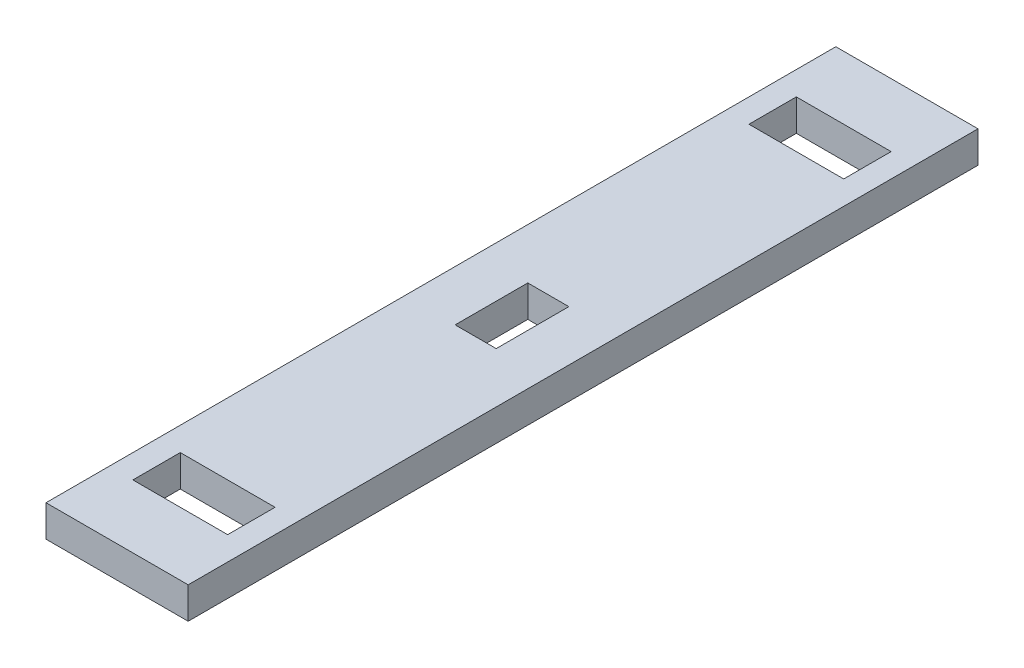
SolidWorks part; units mm, degrees
ref_plane "Plan de face" through (0, 0, 0) normal (0, 0, 1) x (1, 0, 0)
ref_plane "Plan de dessus" through (0, 0, 0) normal (0, 1, 0) x (1, 0, 0)
ref_plane "Plan de droite" through (0, 0, 0) normal (1, 0, 0) x (0, 0, -1)
sketch "Esquisse1" plane through (0, 0, 0) normal (0, 1, 0) x (1, 0, 0)
  line L0 (3.409, -1.8775) -> (3.409, 2.1225) construction
  line L1 (-1.091, 48.1225) -> (7.909, 48.1225)
  line L2 (-1.091, 48.1225) -> (-1.091, -1.8775)
  line L3 (-1.091, -1.8775) -> (7.909, -1.8775)
  line L4 (7.909, 48.1225) -> (7.909, -1.8775)
  line L5 (0.409, 2.1225) -> (6.409, 2.1225)
  line L6 (0.409, 2.1225) -> (0.409, 5.1225)
  line L7 (0.409, 5.1225) -> (6.409, 5.1225)
  line L8 (6.409, 2.1225) -> (6.409, 5.1225)
  line L9 (-1.091, 23.1225) -> (7.909, 23.1225) construction
  line L10 (0.409, 41.1225) -> (6.409, 41.1225)
  line L11 (6.409, 44.1225) -> (6.409, 41.1225)
  line L12 (0.409, 44.1225) -> (6.409, 44.1225)
  line L13 (0.409, 44.1225) -> (0.409, 41.1225)
  dimension "D1" = 50
  dimension "D2" = 9
  dimension "D3" = 4
  dimension "D4" = 6
  dimension "D5" = 3
extrude "Boss.-Extru.1" add sketch "Esquisse1" along normal blind 2 contours L4 L1 L2 L3 L13 L12 L11 L10 L8 L5 L6 L7 region at (3.409, 0, -23.1225)
sketch "Esquisse2" plane through (0, 0, 0) normal (0, -1, 0) x (1, 0, 0)
  line L0 (-1.091, -23.1225) -> (7.909, -23.1225) construction
  line L1 (-1.091, -48.1225) -> (-1.091, 1.8775) construction
  line L2 (7.909, -48.1225) -> (7.909, 1.8775) construction
  line L4 (4.709, -25.4225) -> (2.109, -25.4225)
  line L5 (4.709, -25.4225) -> (4.709, -20.8225)
  line L6 (4.709, -20.8225) -> (2.109, -20.8225)
  line L7 (2.109, -25.4225) -> (2.109, -20.8225)
  line L8 (4.709, -25.4225) -> (2.109, -20.8225) construction
  line L9 (4.709, -20.8225) -> (2.109, -25.4225) construction
  point P6 (3.409, -23.1225)
  point P11 (3.409, -23.1225)
  dimension "D1" = 4.6
  dimension "D2" = 2.6
extrude "Enlèv. mat.-Extru.1" cut sketch "Esquisse2" along normal through all and the other way through all contours L7 L4 L5 L6 region at (3.409, 0, -23.1225)
